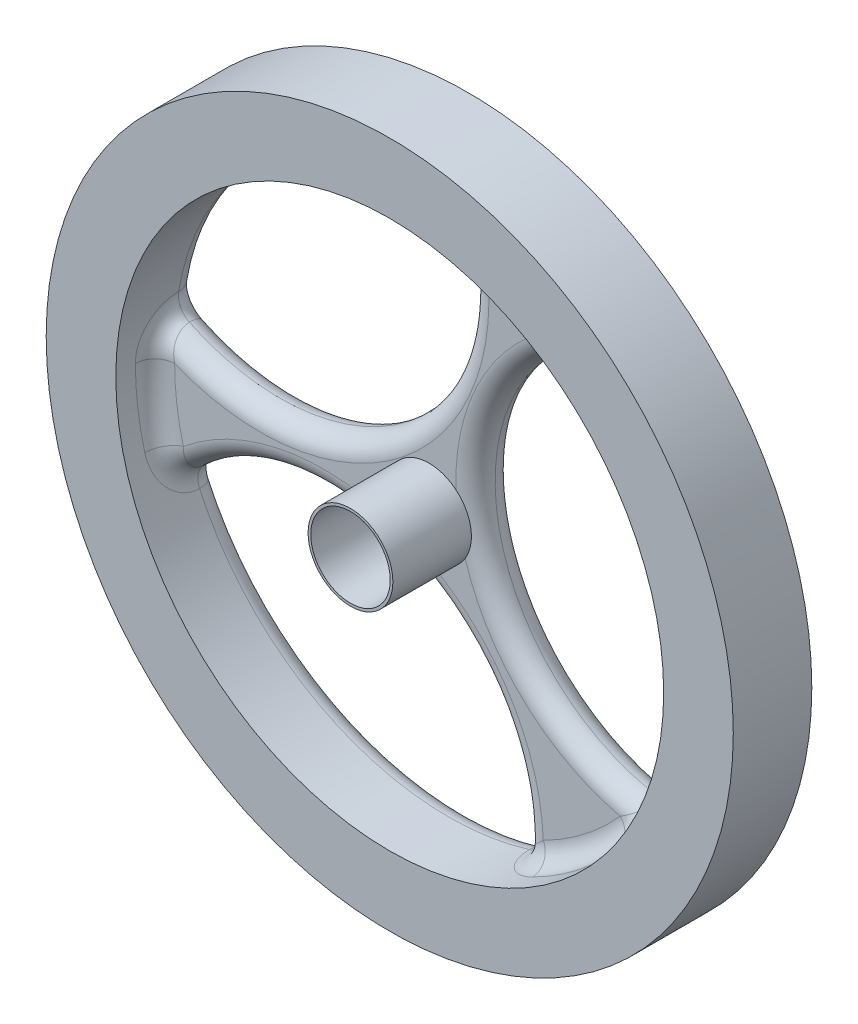
SolidWorks part; units mm, degrees
material "PVC Rigid"
ref_plane "Front Plane" through (0, 0, 0) normal (0, 0, 1) x (1, 0, 0)
ref_plane "Top Plane" through (0, 0, 0) normal (0, 1, 0) x (1, 0, 0)
ref_plane "Right Plane" through (0, 0, 0) normal (1, 0, 0) x (0, 0, -1)
sketch "Sketch1" plane through (0, 0, 0) normal (0, 0, 1) x (1, 0, 0)
  circle A0 centre (0, 0) radius 44.45
extrude "Boss-Extrude1" add sketch "Sketch1" along normal blind 10.16
sketch "Sketch2" plane through (0, 0, 10.16) normal (0, 0, 1) x (1, 0, 0)
  circle A0 centre (0, 0) radius 35.4454
extrude "Cut-Extrude1" cut sketch "Sketch2" against normal blind 5.08
sketch "Sketch3" plane through (0, 0, 5.08) normal (0, 0, 1) x (1, 0, 0)
  arc A1 (4.127, 35.2043) -> (-35.2073, 4.1012) centre (-21.8348, 27.6132) cw
  arc A2 (-32.9145, -13.1533) -> (12.1132, -33.3113) centre (-13.6355, -30.4582) cw
  arc A3 (29.3468, -19.8781) -> (21.2971, 28.3339) centre (31.1604, 5.2027) cw
  arc A4 (-35.2073, 4.1012) -> (4.127, 35.2043) centre (0, 0) cw
  arc A5 (21.2971, 28.3339) -> (29.3468, -19.8781) centre (0, 0) cw
  arc A6 (-32.9145, -13.1533) -> (12.1132, -33.3113) centre (0, 0) ccw
extrude "Cut-Extrude2" cut sketch "Sketch3" against normal through all
fillet "Fillet1" radius 2.54 12 edges at (34.9614, 5.8373, 0) (21.791, -27.9558, 5.08) (-14.4831, -32.3514, 0) (-35.1365, -4.669, 5.08) (-21.9852, 27.8034, 0) (13.168, 32.9086, 5.08) (6.3575, 1.0615, 0) (6.3575, 1.0615, 5.08) (-3.0501, -6.8132, 0) (-3.0501, -6.8132, 5.08) (-5.0577, 6.3961, 0) (-5.0577, 6.3961, 5.08)
sketch "Sketch4" plane through (0, 0, 5.08) normal (0, 0, 1) x (1, 0, 0)
  circle A0 centre (0, 0) radius 5.4843
extrude "Boss-Extrude2" add sketch "Sketch4" along normal blind 10.16
sketch "Sketch5" plane through (0, 0, 15.24) normal (0, 0, 1) x (1, 0, 0)
  circle A0 centre (0, 0) radius 5.145
extrude "Cut-Extrude3" cut sketch "Sketch5" against normal blind 10.16
